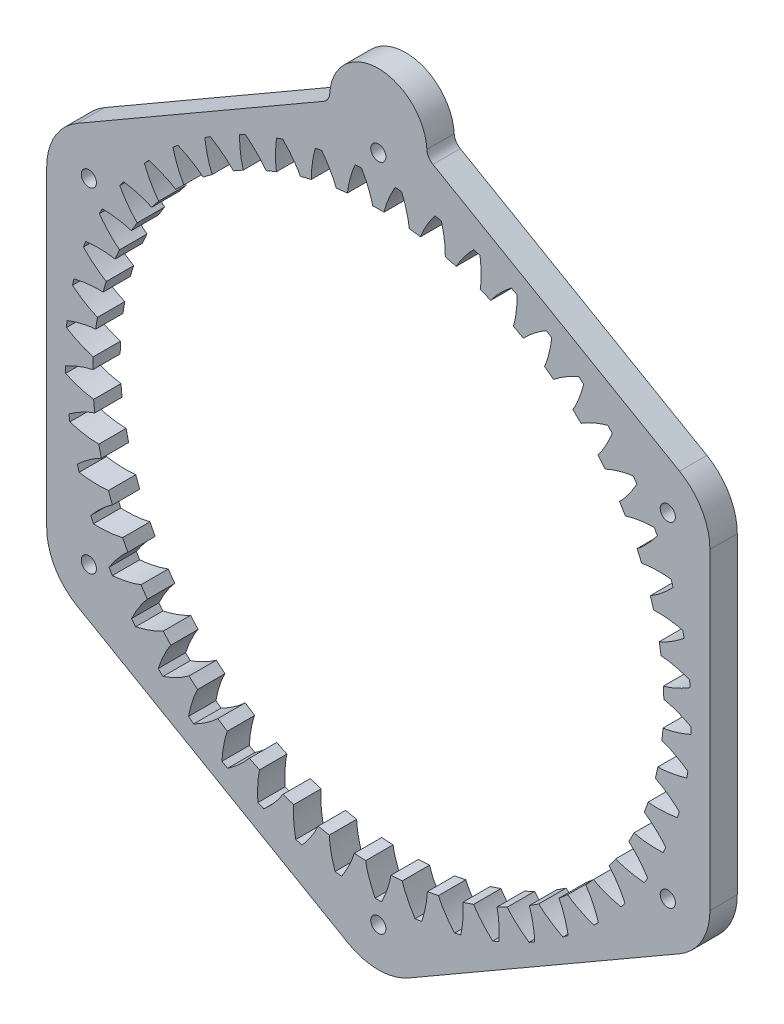
SolidWorks part; units mm, degrees
ref_plane "前视基准面" through (0, 0, 0) normal (0, 0, 1) x (1, 0, 0)
ref_plane "上视基准面" through (0, 0, 0) normal (0, 1, 0) x (1, 0, 0)
ref_plane "右视基准面" through (0, 0, 0) normal (1, 0, 0) x (0, 0, -1)
sketch "草图1" plane through (0, 0, 0) normal (0, 0, 1) x (1, 0, 0)
  circle A0 centre (0, 0) radius 51.5
  circle A1 centre (0, 0) radius 56
extrude "凸台-拉伸1" add sketch "草图1" along normal blind 4.5
ref_axis "基准轴1" through (0, 0, -0.25) along (0, 0, 1)
sketch "草图2" plane through (0, 0, 0) normal (0, 0, 1) x (1, 0, 0)
  line L0 (0, 0) -> (0, 47) construction
  arc A0 (0.9316, 46.9652) -> (-0.9316, 46.9652) centre (0, 0) ccw
  arc A1 (3.2689, 52.2698) -> (-3.2689, 52.2698) centre (0, 0) ccw
  arc A2 (-3.2689, 52.2698) -> (3.2689, 52.2698) centre (0, 0) ccw construction
  spline S0 degree 3 poles (0.9316, 46.9652) (0.9612, 47.0982) (1.0121, 47.3056) (1.0912, 47.592) (1.1627, 47.832) (1.2446, 48.0881) (1.3375, 48.3599) (1.4422, 48.6472) (1.5592, 48.9494) (1.6892, 49.2663) (1.8329, 49.5974) (1.9908, 49.9424) (2.1636, 50.3007) (2.3518, 50.6719) (2.5561, 51.0555) (2.8566, 51.5937) (3.099, 51.9981) (3.2689, 52.2698) knots 0 0 0 0 0.070201 0.110046 0.153054 0.199225 0.24856 0.301057 0.356718 0.415541 0.477528 0.542677 0.61099 0.682466 0.757105 0.834907 1 1 1 1
  spline S1 degree 3 poles (-0.9316, 46.9652) (-0.9612, 47.0982) (-1.0121, 47.3056) (-1.0912, 47.592) (-1.1627, 47.832) (-1.2446, 48.0881) (-1.3375, 48.3599) (-1.4422, 48.6472) (-1.5592, 48.9494) (-1.6892, 49.2663) (-1.8329, 49.5974) (-1.9908, 49.9424) (-2.1636, 50.3007) (-2.3518, 50.6719) (-2.5561, 51.0555) (-2.8566, 51.5937) (-3.099, 51.9981) (-3.2689, 52.2698) knots 0 0 0 0 0.070201 0.110046 0.153054 0.199225 0.24856 0.301057 0.356718 0.415541 0.477528 0.542677 0.61099 0.682466 0.757105 0.834907 1 1 1 1
extrude "凸台-拉伸2" add sketch "草图2" along normal blind 5
pattern_circular "阵列(圆周)1" count 49 every 7.347 about axis through (0, 0, -0.25) along (0, 0, 1) of "凸台-拉伸2"
sketch "草图3" plane through (0, 0, 0) normal (0, 0, 1) x (1, 0, 0)
  circle A0 centre (0, 0) radius 49 construction
  dimension "Dn" = 98
sketch "草图4" plane through (0, 0, 4.5) normal (0, 0, 1) x (1, 0, 0)
  circle A0 centre (0, 0) radius 63
  circle A1 centre (0, 0) radius 56
  circle A2 centre (0, 0) radius 56 construction
  dimension "D1" = 126
extrude "凸台-拉伸3" add sketch "草图4" against normal blind 4.5
sketch "草图5" plane through (0, 0, 4.5) normal (0, 0, 1) x (1, 0, 0)
  line L1 (0, 55) -> (-47.6314, 27.5) construction
  line L2 (-47.6314, 27.5) -> (-47.6314, -27.5) construction
  line L3 (-47.6314, -27.5) -> (0, -55) construction
  line L4 (0, -55) -> (47.6314, -27.5) construction
  line L5 (47.6314, -27.5) -> (47.6314, 27.5) construction
  line L6 (47.6314, 27.5) -> (0, 55) construction
  circle A0 centre (0, 0) radius 55 construction
  circle A1 centre (0, 0) radius 47.6314 construction
  circle A2 centre (0, 55) radius 1.25
  circle A3 centre (47.6314, 27.5) radius 1.25
  circle A4 centre (47.6314, -27.5) radius 1.25
  circle A5 centre (0, -55) radius 1.25
  circle A6 centre (-47.6314, -27.5) radius 1.25
  circle A7 centre (-47.6314, 27.5) radius 1.25
  point P24 (0, 0)
  dimension "D1" = 110
  dimension "D3" = 2.5
  dimension "D2" = 6
extrude "切除-拉伸1" cut sketch "草图5" against normal up to next
cosmetic thread "装饰螺纹线13" parameters "D2"=3
cosmetic thread "装饰螺纹线14" parameters "D2"=3
cosmetic thread "装饰螺纹线15" parameters "D2"=3
cosmetic thread "装饰螺纹线16" parameters "D2"=3
cosmetic thread "装饰螺纹线17" parameters "D2"=3
cosmetic thread "装饰螺纹线18" parameters "D2"=3
sketch "草图7" plane through (0, 0, 4.5) normal (0, 0, 1) x (1, 0, 0)
  circle A0 centre (0, 55) radius 3
  circle A1 centre (47.6314, 27.5) radius 3
  circle A2 centre (47.6314, -27.5) radius 3
  circle A3 centre (0, -55) radius 3
  circle A4 centre (-47.6314, -27.5) radius 3
  circle A5 centre (-47.6314, 27.5) radius 3
  dimension "D1" = 6
sketch "草图8" plane through (0, 0, 0) normal (0, 0, -1) x (-1, 0, 0)
  circle A0 centre (0, 55) radius 3
  circle A1 centre (47.6314, 27.5) radius 3
  circle A2 centre (47.6314, -27.5) radius 3
  circle A3 centre (0, -55) radius 3
  circle A4 centre (-47.6314, -27.5) radius 3
  circle A5 centre (-47.6314, 27.5) radius 3
  dimension "D1" = 6
extrude "切除-拉伸4" cut sketch "草图8" against normal blind 2.5
sketch "草图9" plane through (0, 0, 0) normal (0, 0, -1) x (-1, 0, 0)
  line L7 (0, 63) -> (-54.5596, 31.5)
  line L8 (-54.5596, 31.5) -> (-54.5596, -31.5)
  line L9 (-54.5596, -31.5) -> (0, -63)
  line L10 (0, -63) -> (54.5596, -31.5)
  line L11 (54.5596, -31.5) -> (54.5596, 31.5)
  line L12 (54.5596, 31.5) -> (0, 63)
  circle A0 centre (0, 0) radius 54.5596 construction
  circle A2 centre (0, 0) radius 63 construction
  circle A3 centre (0, 0) radius 63
extrude "切除-拉伸5" cut sketch "草图9" against normal blind 10 contours L8 A3 | L9 A3 | L10 A3 | L11 A3 | L12 A3 | L7 A3 region at (-28.978, 50.1913, 0) region at (28.978, 50.1913, 0) region at (57.9559, 0, 0) region at (-57.9559, 0, 0) region at (28.978, -50.1913, 0) region at (-28.978, -50.1913, 0)
fillet "圆角1" radius 10 6 edges at (54.5596, -31.5, 2.25) (0, -63, 2.25) (-54.5596, -31.5, 2.25) (-54.5596, 31.5, 2.25) (0, 63, 2.25) (54.5596, 31.5, 2.25)
sketch "草图10" plane through (0, 0, 0) normal (0, 0, -1) x (-1, 0, 0)
  line L0 (0, 55) -> (0, 59) construction
  line L1 (-8, 57.453) -> (-8, 59)
  line L2 (8, 57.453) -> (8, 59)
  line L3 (8, 52.0867) -> (8, 57.453) construction
  line L4 (-8, 52.0867) -> (-8, 57.453) construction
  arc A0 (-8, 52.0867) -> (8, 52.0867) centre (0, 55) ccw construction
  arc A1 (8, 59) -> (-8, 59) centre (0, 59) ccw
  arc A2 (8, 57.453) -> (-8, 57.453) centre (0, 51.453) ccw
  arc A3 (5, 60.1132) -> (-5, 60.1132) centre (0, 51.453) ccw construction
  arc A4 (-8, 57.453) -> (8, 57.453) centre (0, 51.453) ccw construction
  point P4 (0, 57)
  dimension "D1" = 8
  dimension "8" = 4
extrude "凸台-拉伸4" add sketch "草图10" against normal blind 5
sketch "草图11" plane through (0, 0, 0) normal (0, 0, -1) x (-1, 0, 0)
  circle A0 centre (0, 0) radius 63 construction
  circle A1 centre (0, 63) radius 3.05
  dimension "D1" = 126
  dimension "D2" = 6.1
extrude "切除-拉伸6" cut sketch "草图11" against normal blind 3.5
fillet "圆角2" radius 2 2 edges at (8, 58.3812, 2.25) (-8, 58.3812, 2.25)
fillet "圆角3" radius 0.5 1 edges at (-3.05, 63, 0) first distance on face at (-3.05, 63, 0)
sketch "草图12" plane through (0, 0, 5) normal (0, 0, 1) x (1, 0, 0)
  circle A0 centre (0, 0) radius 52.3719
extrude "切除-拉伸7" cut sketch "草图12" against normal blind 0.5
sketch "草图13" plane through (0, 0, 5) normal (0, 0, 1) x (1, 0, 0)
  circle A0 centre (0, 55) radius 12.5
  dimension "D1" = 25
extrude "切除-拉伸8" cut sketch "草图13" against normal blind 0.5
